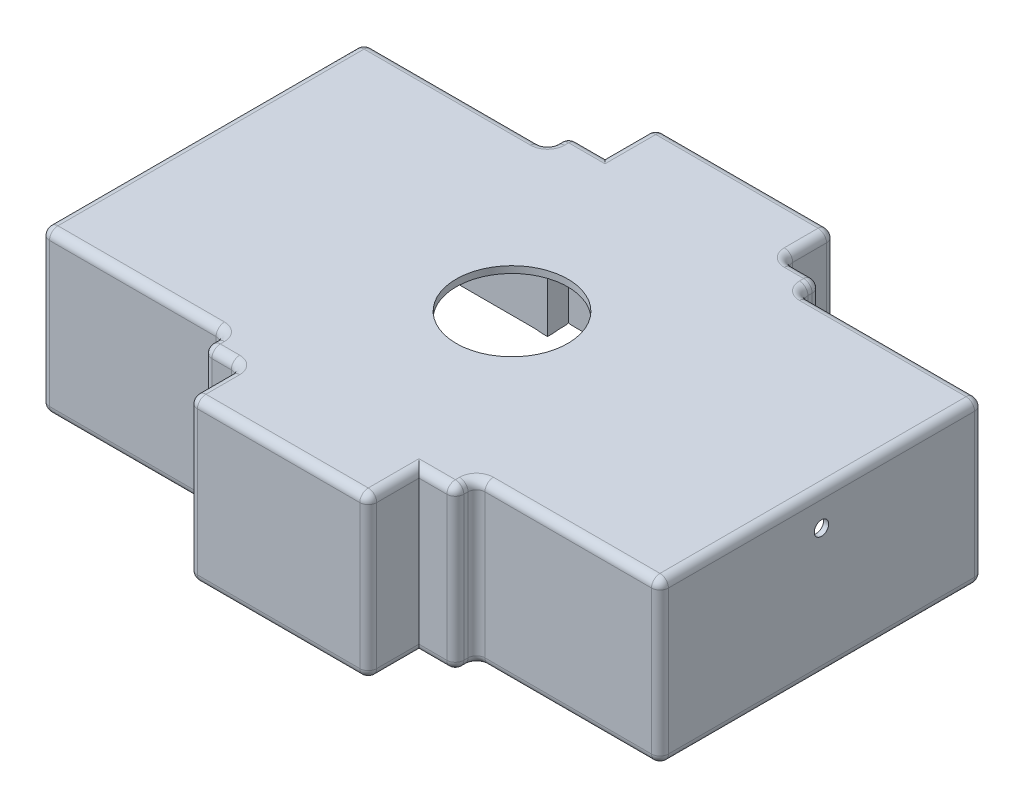
SolidWorks part; units mm, degrees
material "ABS"
ref_plane "Front Plane" through (0, 0, 0) normal (0, 0, 1) x (1, 0, 0)
ref_plane "Top Plane" through (0, 0, 0) normal (0, 1, 0) x (1, 0, 0)
ref_plane "Right Plane" through (0, 0, 0) normal (1, 0, 0) x (0, 0, -1)
sketch "Sketch1" plane through (0, 0, 0) normal (0, 1, 0) x (1, 0, 0)
  line L0 (3.1563, 78.9084) -> (3.1563, -96.1468) construction
  line L1 (-115.3277, -7.5266) -> (136.4508, -7.5266) construction
  line L2 (-68.3437, 84.9734) -> (-176.8437, 84.9734)
  line L3 (183.1563, 84.9734) -> (183.1563, -100.0266)
  line L4 (-68.3437, 84.9734) -> (-68.3437, 97.4734)
  line L5 (74.6563, 84.9734) -> (74.6563, 97.4734)
  line L6 (74.6563, 84.9734) -> (183.1563, 84.9734)
  line L7 (-68.3437, -100.0266) -> (-176.8437, -100.0266)
  line L8 (-68.3437, -100.0266) -> (-68.3437, -112.5266)
  line L9 (74.6563, -100.0266) -> (74.6563, -112.5266)
  line L10 (74.6563, -100.0266) -> (183.1563, -100.0266)
  line L11 (-176.8437, 84.9734) -> (-176.8437, -100.0266)
  line L12 (53.1563, -112.5266) -> (53.1563, -142.5266)
  line L13 (53.1563, -142.5266) -> (-46.8437, -142.5266)
  line L14 (-46.8437, -142.5266) -> (-46.8437, -112.5266)
  line L15 (53.1563, -112.5266) -> (74.6563, -112.5266)
  line L16 (-68.3437, -112.5266) -> (-46.8437, -112.5266)
  line L17 (-68.3437, 97.4734) -> (-46.8437, 97.4734)
  line L18 (-46.8437, 127.4734) -> (-46.8437, 97.4734)
  line L19 (53.1563, 127.4734) -> (-46.8437, 127.4734)
  line L20 (53.1563, 97.4734) -> (53.1563, 127.4734)
  line L21 (53.1563, 97.4734) -> (74.6563, 97.4734)
  line L22 (-71.3437, 87.9734) -> (-179.8437, 87.9734)
  line L23 (-179.8437, 87.9734) -> (-179.8437, -103.0266)
  line L24 (-71.3437, -103.0266) -> (-179.8437, -103.0266)
  line L25 (-71.3437, -103.0266) -> (-71.3437, -115.5266)
  line L26 (-71.3437, -115.5266) -> (-49.8437, -115.5266)
  line L27 (-49.8437, -145.5266) -> (-49.8437, -115.5266)
  line L28 (56.1563, -145.5266) -> (-49.8437, -145.5266)
  line L29 (56.1563, -115.5266) -> (56.1563, -145.5266)
  line L30 (56.1563, -115.5266) -> (77.6563, -115.5266)
  line L31 (77.6563, -103.0266) -> (77.6563, -115.5266)
  line L32 (77.6563, -103.0266) -> (186.1563, -103.0266)
  line L33 (186.1563, 87.9734) -> (186.1563, -103.0266)
  line L34 (77.6563, 87.9734) -> (186.1563, 87.9734)
  line L35 (77.6563, 87.9734) -> (77.6563, 100.4734)
  line L36 (56.1563, 100.4734) -> (77.6563, 100.4734)
  line L37 (56.1563, 100.4734) -> (56.1563, 130.4734)
  line L38 (56.1563, 130.4734) -> (-49.8437, 130.4734)
  line L39 (-49.8437, 130.4734) -> (-49.8437, 100.4734)
  line L40 (-71.3437, 100.4734) -> (-49.8437, 100.4734)
  line L41 (-71.3437, 87.9734) -> (-71.3437, 100.4734)
  circle A28 centre (-36.8437, -132.5266) radius 5
  circle A29 centre (43.1563, -132.5266) radius 5
  circle A30 centre (43.1563, 117.4734) radius 5
  circle A31 centre (-36.8437, 117.4734) radius 5
  point P48 (-68.3437, 84.9734)
  dimension "D2" = 3.1563
  dimension "D1" = 10
  dimension "D3" = 43.1563
  dimension "D4" = 53.1563
  dimension "D5" = 56.1563
  dimension "D6" = 74.6563
  dimension "D7" = 186.1563
  dimension "D8" = 84.9734
  dimension "D9" = 97.4734
  dimension "D10" = 117.4734
  dimension "D11" = 127.4734
  dimension "D12" = 7.5266
extrude "Boss-Extrude1" add sketch "Sketch1" along normal blind 91 contours L41 L22 L23 L24 L25 L26 L27 L28 L29 L30 L31 L32 L33 L34 L35 L36 L37 L38 L39 L40 L20 L21 L5 L6 L3 L10 L9 L15 L12 L13 L14 L16 L8 L7 L11 L2 L4 L17 L18 L19 region at (-70.8853, 0, -94.2234)
sketch "Sketch4" plane through (0, 91, 0) normal (0, 1, 0) x (1, 0, 0)
  line L20 (-71.3437, 100.4734) -> (-71.3437, 87.9734)
  line L21 (-71.3437, 87.9734) -> (-179.8437, 87.9734)
  line L22 (-179.8437, 87.9734) -> (-179.8437, -103.0266)
  line L23 (-179.8437, -103.0266) -> (-71.3437, -103.0266)
  line L24 (-71.3437, -103.0266) -> (-71.3437, -115.5266)
  line L25 (-71.3437, -115.5266) -> (-49.8437, -115.5266)
  line L26 (-49.8437, -115.5266) -> (-49.8437, -145.5266)
  line L27 (-49.8437, -145.5266) -> (56.1563, -145.5266)
  line L28 (56.1563, -145.5266) -> (56.1563, -115.5266)
  line L29 (56.1563, -115.5266) -> (77.6563, -115.5266)
  line L30 (77.6563, -115.5266) -> (77.6563, -103.0266)
  line L31 (77.6563, -103.0266) -> (186.1563, -103.0266)
  line L32 (186.1563, -103.0266) -> (186.1563, 87.9734)
  line L33 (186.1563, 87.9734) -> (77.6563, 87.9734)
  line L34 (77.6563, 87.9734) -> (77.6563, 100.4734)
  line L35 (77.6563, 100.4734) -> (56.1563, 100.4734)
  line L36 (56.1563, 100.4734) -> (56.1563, 130.4734)
  line L37 (56.1563, 130.4734) -> (-49.8437, 130.4734)
  line L38 (-49.8437, 130.4734) -> (-49.8437, 100.4734)
  line L39 (-49.8437, 100.4734) -> (-71.3437, 100.4734)
  line L40 (-71.3437, 100.4734) -> (-71.3437, 87.9734)
  line L41 (-71.3437, 87.9734) -> (-179.8437, 87.9734)
  line L42 (-179.8437, 87.9734) -> (-179.8437, -103.0266)
  line L43 (-179.8437, -103.0266) -> (-71.3437, -103.0266)
  line L44 (-71.3437, -103.0266) -> (-71.3437, -115.5266)
  line L45 (-71.3437, -115.5266) -> (-49.8437, -115.5266)
  line L46 (-49.8437, -115.5266) -> (-49.8437, -145.5266)
  line L47 (-49.8437, -145.5266) -> (56.1563, -145.5266)
  line L48 (56.1563, -145.5266) -> (56.1563, -115.5266)
  line L49 (56.1563, -115.5266) -> (77.6563, -115.5266)
  line L50 (77.6563, -115.5266) -> (77.6563, -103.0266)
  line L51 (77.6563, -103.0266) -> (186.1563, -103.0266)
  line L52 (186.1563, -103.0266) -> (186.1563, 87.9734)
  line L53 (186.1563, 87.9734) -> (77.6563, 87.9734)
  line L54 (77.6563, 87.9734) -> (77.6563, 100.4734)
  line L55 (77.6563, 100.4734) -> (56.1563, 100.4734)
  line L56 (56.1563, 100.4734) -> (56.1563, 130.4734)
  line L57 (56.1563, 130.4734) -> (-49.8437, 130.4734)
  line L58 (-49.8437, 130.4734) -> (-49.8437, 100.4734)
  line L59 (-49.8437, 100.4734) -> (-71.3437, 100.4734)
  dimension "D1" = 0
extrude "Boss-Extrude3" add sketch "Sketch4" along normal blind 4
sketch "Sketch5" plane through (0, 0, 0) normal (0, -1, 0) x (1, 0, 0)
  line L3 (-179.8437, 7.5266) -> (-101.7455, 7.5266) construction
  line L4 (-46.8437, 112.5266) -> (53.1563, 112.5266)
  line L5 (53.1563, -97.4734) -> (-46.8437, -97.4734)
  line L6 (-179.8437, -87.9734) -> (-179.8437, 103.0266) construction
  line L7 (-71.3437, -87.9734) -> (-179.8437, -87.9734) construction
  line L8 (-16.8437, 142.5266) -> (-16.8437, 112.5266)
  line L10 (3.1563, -97.4734) -> (23.1563, -97.4734)
  line L11 (23.1563, -97.4734) -> (23.1563, -127.4734)
  line L12 (53.1563, -127.4734) -> (-46.8437, -127.4734) construction
  line L13 (23.1563, -127.4734) -> (-16.8437, -127.4734)
  line L14 (-16.8437, -127.4734) -> (-16.8437, -97.4734)
  line L15 (23.1563, 112.5266) -> (23.1563, 142.5266)
  line L20 (-71.3437, -87.9734) -> (-71.3437, -100.4734)
  line L21 (-71.3437, -100.4734) -> (-49.8437, -100.4734)
  line L22 (-49.8437, -100.4734) -> (-49.8437, -130.4734)
  line L23 (-49.8437, -130.4734) -> (56.1563, -130.4734)
  line L24 (56.1563, -130.4734) -> (56.1563, -100.4734)
  line L25 (56.1563, -100.4734) -> (77.6563, -100.4734)
  line L26 (77.6563, -100.4734) -> (77.6563, -87.9734)
  line L27 (77.6563, -87.9734) -> (186.1563, -87.9734)
  line L28 (186.1563, -87.9734) -> (186.1563, 103.0266)
  line L29 (186.1563, 103.0266) -> (77.6563, 103.0266)
  line L30 (77.6563, 103.0266) -> (77.6563, 115.5266)
  line L31 (77.6563, 115.5266) -> (56.1563, 115.5266)
  line L32 (56.1563, 115.5266) -> (56.1563, 145.5266)
  line L33 (56.1563, 145.5266) -> (-49.8437, 145.5266)
  line L34 (-49.8437, 145.5266) -> (-49.8437, 115.5266)
  line L35 (-49.8437, 115.5266) -> (-71.3437, 115.5266)
  line L36 (-71.3437, 115.5266) -> (-71.3437, 103.0266)
  line L37 (-71.3437, 103.0266) -> (-179.8437, 103.0266)
  line L38 (-179.8437, 103.0266) -> (-179.8437, -87.9734)
  line L39 (-179.8437, -87.9734) -> (-71.3437, -87.9734)
  line L40 (-71.3437, -87.9734) -> (-71.3437, -100.4734)
  line L41 (-71.3437, -100.4734) -> (-49.8437, -100.4734)
  line L42 (-49.8437, -100.4734) -> (-49.8437, -130.4734)
  line L43 (-49.8437, -130.4734) -> (56.1563, -130.4734)
  line L44 (56.1563, -130.4734) -> (56.1563, -100.4734)
  line L45 (56.1563, -100.4734) -> (77.6563, -100.4734)
  line L46 (77.6563, -100.4734) -> (77.6563, -87.9734)
  line L47 (77.6563, -87.9734) -> (186.1563, -87.9734)
  line L48 (186.1563, -87.9734) -> (186.1563, 103.0266)
  line L49 (186.1563, 103.0266) -> (77.6563, 103.0266)
  line L50 (77.6563, 103.0266) -> (77.6563, 115.5266)
  line L51 (77.6563, 115.5266) -> (56.1563, 115.5266)
  line L52 (56.1563, 115.5266) -> (56.1563, 145.5266)
  line L53 (56.1563, 145.5266) -> (-49.8437, 145.5266)
  line L54 (-49.8437, 145.5266) -> (-49.8437, 115.5266)
  line L55 (-49.8437, 115.5266) -> (-71.3437, 115.5266)
  line L56 (-71.3437, 115.5266) -> (-71.3437, 103.0266)
  line L57 (-71.3437, 103.0266) -> (-179.8437, 103.0266)
  line L58 (-179.8437, 103.0266) -> (-179.8437, -87.9734)
  line L59 (-179.8437, -87.9734) -> (-71.3437, -87.9734)
  circle A0 centre (43.1563, 132.5266) radius 5
  circle A1 centre (-36.8437, 132.5266) radius 5
  circle A2 centre (43.1563, -117.4734) radius 5
  circle A3 centre (-36.8437, -117.4734) radius 5
  point P2 (43.1563, 132.5266)
  point P8 (-36.8437, 132.5266)
  line M80 (53.1563, -97.4734) -> (53.1563, -127.4734)
  line M81 (53.1563, -127.4734) -> (-46.8437, -127.4734)
  line M82 (-46.8437, -127.4734) -> (-46.8437, -97.4734)
  line M90 (-46.8437, 112.5266) -> (-46.8437, 142.5266)
  line M91 (-46.8437, 142.5266) -> (53.1563, 142.5266)
  line M92 (53.1563, 142.5266) -> (53.1563, 112.5266)
  dimension "D1" = 0
extrude "Boss-Extrude4" add sketch "Sketch5" against normal blind 5 contours L15 L4 A0 M92 M91 | L8 L4 A1 M91 M90 | L5 L11 A2 M81 M80 | L14 L5 A3 M81 M82 region at (-31.3656, 0, 127.0486) region at (37.6783, 0, 127.0486) region at (37.6783, 0, -111.9953) region at (-31.3656, 0, -111.9953)
sketch "Sketch6" plane through (0, 95, 0) normal (0, 1, 0) x (1, 0, 0)
  line L0 (3.1563, 130.4734) -> (3.1563, -145.5266) construction
  line L1 (56.1563, 130.4734) -> (-49.8437, 130.4734) construction
  line L2 (-49.8437, -145.5266) -> (56.1563, -145.5266) construction
  line L3 (186.1563, -7.5266) -> (-179.8437, -7.5266) construction
  line L4 (186.1563, -103.0266) -> (186.1563, 87.9734) construction
  line L5 (-179.8437, 87.9734) -> (-179.8437, -103.0266) construction
  circle A0 centre (3.1563, -7.5266) radius 33
  dimension "D1" = 66
extrude "Cut-Extrude1" cut sketch "Sketch6" against normal blind 5 contours A0
sketch "Sketch8" plane through (186.1563, 0, 0) normal (1, 0, 0) x (0, 0, -1)
  line L0 (87.9734, 0) -> (-103.0266, 0) construction
  circle A0 centre (-7.5266, 75.45) radius 4.25
  dimension "D1" = 8.5
  dimension "D2" = 95.5
  dimension "D3" = 75.45
extrude "Cut-Extrude2" cut sketch "Sketch8" against normal blind 5
fillet "Fillet4" radius 5 20 edges at (77.6563, 47.5, 103.0266) (77.6563, 47.5, 115.5266) (53.1563, 48, 112.5266) (56.1563, 47.5, 145.5266) (-49.8437, 47.5, 145.5266) (-49.8437, 47.5, 115.5266) (-71.3437, 47.5, 115.5266) (-71.3437, 47.5, 103.0266) (-179.8437, 47.5, 103.0266) (-179.8437, 47.5, -87.9734) (-71.3437, 47.5, -87.9734) (-71.3437, 47.5, -100.4734) (-46.8437, 48, -97.4734) (-49.8437, 47.5, -130.4734) (56.1563, 47.5, -130.4734) (56.1563, 47.5, -100.4734) (77.6563, 47.5, -100.4734) (77.6563, 47.5, -87.9734) (186.1563, 47.5, -87.9734) (186.1563, 47.5, 103.0266)
fillet "Fillet5" radius 5 38 edges at (-58.0937, 95, -100.4734) (-69.8792, 95, -99.0089) (-71.3437, 95, -94.2234) (-72.8081, 95, -89.4378) (56.1563, 95, 128.0266) (54.6919, 95, 144.0622) (-48.3792, 95, 144.0622) (-49.8437, 95, 130.5266) (-51.3081, 95, 116.9911) (-60.5937, 95, 115.5266) (-69.8792, 95, 114.0622) (-71.3437, 95, 109.2766) (-72.8081, 95, 104.4911) (-178.3792, 95, 101.5622) (-178.3792, 95, -86.5089) (64.4063, 95, 115.5266) (76.1919, 95, 114.0622) (77.6563, 95, 109.2766) (79.1208, 95, 104.4911) (131.9063, 95, 103.0266) (184.6919, 95, 101.5622) (-49.8437, 95, -112.9734) (-48.3792, 95, -129.0089) (54.6919, 95, -129.0089) (56.1563, 95, -115.4734) (57.6208, 95, -101.9378) (66.9063, 95, -100.4734) (76.1919, 95, -99.0089) (77.6563, 95, -94.2234) (79.1208, 95, -89.4378) (184.6919, 95, -86.5089) (3.1563, 95, 145.5266) (-125.5937, 95, 103.0266) (-179.8437, 95, 7.5266) (-125.5937, 95, -87.9734) (3.1563, 95, -130.4734) (131.9063, 95, -87.9734) (186.1563, 95, 7.5266)
fillet "Fillet6" radius 5 11 edges at (-58.0937, 0, -100.4734) (-69.8792, 0, -99.0089) (-71.3437, 0, -94.2234) (-72.8081, 0, -89.4378) (56.1563, 0, 128.0266) (54.6919, 0, 144.0622) (3.1563, 0, 145.5266) (-48.3792, 0, 144.0622) (-49.8437, 0, 130.5266) (-51.3081, 0, 116.9911) (-72.8081, 0, 104.4911)
fillet "Fillet7" radius 5 11 edges at (-49.8437, 0, -111.4734) (-48.3792, 0, -129.0089) (3.1563, 0, -130.4734) (54.6919, 0, -129.0089) (56.1563, 0, -115.4734) (57.6208, 0, -101.9378) (79.1208, 0, -89.4378) (61.9063, 0, 115.5266) (76.1919, 0, 114.0622) (77.6563, 0, 109.2766) (79.1208, 0, 104.4911)
sketch "Sketch10" plane through (-179.8437, 0, 0) normal (-1, 0, 0) x (0, 0, 1)
  line L0 (-82.9734, 90) -> (-82.9734, 5) construction
  line L1 (-77.9734, 70) -> (88.4666, 70)
  line L2 (-77.9734, 70) -> (-77.9734, 55)
  line L3 (-77.9734, 55) -> (88.4666, 55)
  line L4 (88.4666, 70) -> (88.4666, 55)
  line L5 (98.0266, 90) -> (-82.9734, 90) construction
  line L6 (-82.9734, 5) -> (98.0266, 5) construction
  dimension "D1" = 5
  dimension "D2" = 20
  dimension "D3" = 171.44
  dimension "D4" = 50
extrude "Cut-Extrude3" cut sketch "Sketch10" against normal blind 5
